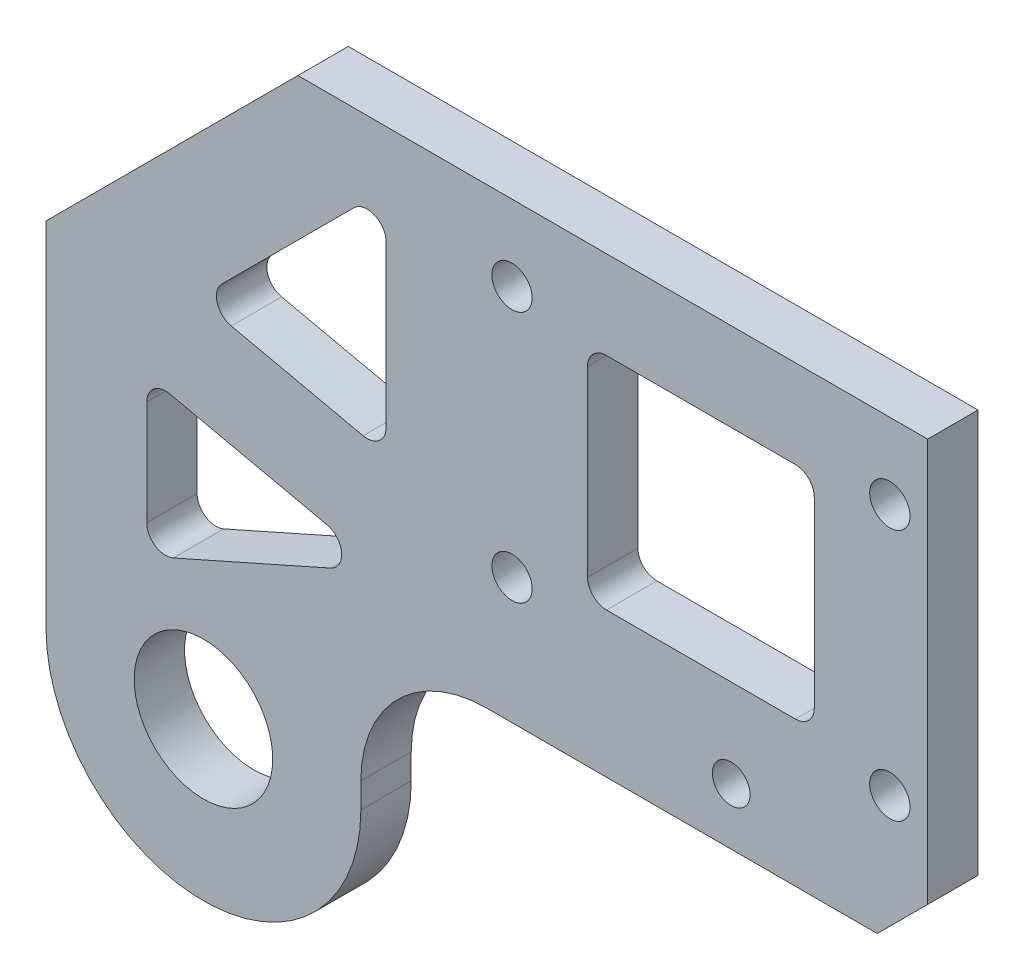
SolidWorks part; units mm, degrees
ref_plane "前视基准面" through (0, 0, 0) normal (0, 0, 1) x (1, 0, 0)
ref_plane "上视基准面" through (0, 0, 0) normal (0, 1, 0) x (1, 0, 0)
ref_plane "右视基准面" through (0, 0, 0) normal (1, 0, 0) x (0, 0, -1)
ref_plane "基准面1" through (0, 0, 0) normal (0, 0, -1) x (-1, 0, 0)
sketch "草图1" plane through (0, 0, 0) normal (0, 0, -1) x (-1, 0, 0)
  line L0 (12.5, -3) -> (12.5, 12)
  line L1 (-17.5, 45) -> (-57.5, 45)
  line L2 (-57.5, 45) -> (-57.5, 9)
  line L3 (-57.5, 9) -> (-22.5, 9)
  line L4 (-12.5, -1) -> (-12.5, -3)
  line L5 (12.5, 12) -> (12.5, 45)
  line L6 (12.5, 45) -> (-17.5, 45)
  circle A0 centre (-54.5, 19) radius 1.6
  circle A1 centre (-24.5, 19) radius 1.6
  circle A2 centre (-24.5, 39) radius 1.6
  circle A3 centre (-54.5, 39) radius 1.6
  circle A4 centre (0, -3) radius 6.075
  arc A6 (-22.5, 9) -> (-12.5, -1) centre (-22.5, -1) cw
  arc A7 (-12.5, -3) -> (12.5, -3) centre (0, -3) ccw
  dimension "D2" = 6
  dimension "D1" = 36
extrude "凸台-拉伸1" add sketch "草图1" against normal blind 4
sketch "草图4" plane through (0, 0, 4) normal (0, 0, 1) x (1, 0, 0)
  line L4 (57.5, 45) -> (57.5, 9) construction
  line L5 (57.5, 9) -> (22.5, 9) construction
  circle A0 centre (41.9036, 13.5) radius 1.5
  dimension "D1" = 3
  dimension "D2" = 15.5964
  dimension "D3" = 4.5
extrude "切除-拉伸3" cut sketch "草图4" against normal up to next
sketch "草图5" plane through (0, 0, 4) normal (0, 0, 1) x (1, 0, 0)
  circle A3 centre (0, -3) radius 6.075
  circle A4 centre (0, -3) radius 5.5
  dimension "D1" = 11
extrude "凸台-拉伸2" add sketch "草图5" against normal blind 4
chamfer "倒角1" distance 20 angle 45 1 edges at (-12.5, 45, 2)
sketch "草图6" plane through (0, 0, 4) normal (0, 0, 1) x (1, 0, 0)
  line L10 (30.5, 36.5) -> (30.5, 22)
  line L12 (32, 20.5) -> (47, 20.5)
  line L13 (48.5, 22) -> (48.5, 36.5)
  line L14 (47, 38) -> (32, 38)
  line L15 (7.5, 45) -> (57.5, 45) construction
  line L16 (11.9393, 38.1256) -> (1.4738, 27.6601)
  line L17 (2.2104, 25.1348) -> (12.676, 22.8195)
  line L18 (14.5, 24.2841) -> (14.5, 37.065)
  line L19 (-4.5, 16.5579) -> (-4.5, 8.2512)
  line L20 (-2.3909, 6.8805) -> (10.0888, 12.4262)
  line L21 (9.8037, 15.2615) -> (-2.676, 18.0225)
  line L22 (7.5, 45) -> (-12.5, 25) construction
  line L23 (-12.5, -3) -> (-12.5, 25) construction
  circle A0 centre (54.5, 39) radius 1.6 construction
  circle A4 centre (24.5, 39) radius 1.6 construction
  circle A8 centre (41.9036, 13.5) radius 1.5 construction
  arc A9 (48.5, 36.5) -> (47, 38) centre (47, 36.5) ccw
  arc A10 (47, 20.5) -> (48.5, 22) centre (47, 22) ccw
  arc A11 (30.5, 22) -> (32, 20.5) centre (32, 22) ccw
  arc A12 (30.5, 36.5) -> (32, 38) centre (32, 36.5) cw
  circle A13 centre (0, -3) radius 5.5 construction
  arc A14 (-4.5, 8.2512) -> (-2.3909, 6.8805) centre (-3, 8.2512) ccw
  arc A15 (-4.5, 16.5579) -> (-2.676, 18.0225) centre (-3, 16.5579) cw
  arc A16 (10.0888, 12.4262) -> (9.8037, 15.2615) centre (9.4796, 13.7969) ccw
  arc A17 (12.676, 22.8195) -> (14.5, 24.2841) centre (13, 24.2841) ccw
  arc A18 (1.4738, 27.6601) -> (2.2104, 25.1348) centre (2.5345, 26.5994) ccw
  arc A19 (14.5, 37.065) -> (11.9393, 38.1256) centre (13, 37.065) ccw
  point P32 (14.5, 14.3864)
  point P33 (-4.5, 18.426)
  dimension "D4" = 7
  dimension "D8" = 8
  dimension "D11" = 1.5
  dimension "D5" = 1.5
  dimension "D1" = 6
  dimension "D2" = 6
  dimension "D3" = 7
  dimension "D6" = 8
  dimension "D7" = 10
  dimension "D9" = 8
  dimension "D10" = 10
extrude "切除-拉伸4" cut sketch "草图6" against normal blind 10
chamfer "Chamfer1" distance 4 angle 45 1 edges at (57.5, 9, 2)
